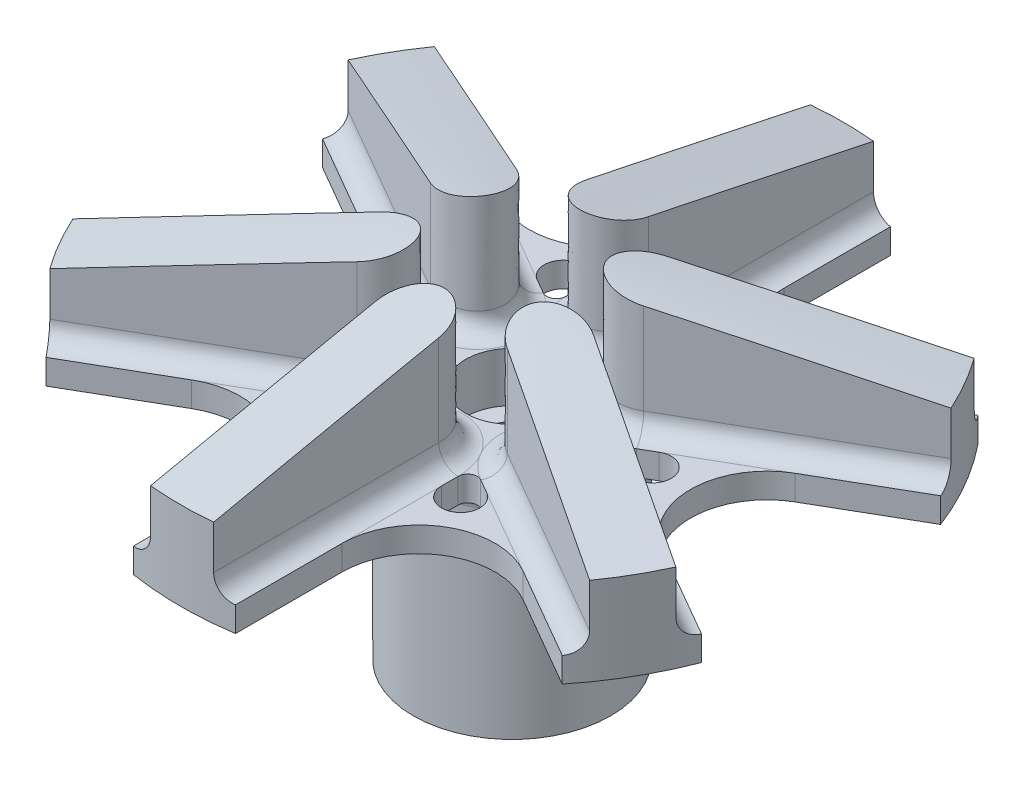
SolidWorks part; units mm, degrees
ref_plane "Front Plane" through (0, 0, 0) normal (0, 0, 1) x (1, 0, 0)
ref_plane "Top Plane" through (0, 0, 0) normal (0, 1, 0) x (1, 0, 0)
ref_plane "Right Plane" through (0, 0, 0) normal (1, 0, 0) x (0, 0, -1)
sketch "Sketch1" plane through (0, 0, 0) normal (0, 1, 0) x (1, 0, 0)
  circle A0 centre (0, 0) radius 26.67
  dimension "D1" = 53.34
extrude "impeller plate" add sketch "Sketch1" along normal blind 2
sketch "Sketch6" plane through (0, 0, 0) normal (0, -1, 0) x (-1, 0, 0)
  circle A0 centre (0, 0) radius 7.9375
  dimension "D1" = 15.875
extrude "boss" add sketch "Sketch6" along normal blind 17
sketch "Sketch7" plane through (0, -17, 0) normal (0, -1, 0) x (-1, 0, 0)
  circle A0 centre (0, 0) radius 2.1828
  dimension "D1" = 4.3656
extrude "bolt bore" cut sketch "Sketch7" against normal through all
sketch "Sketch8" plane through (0, -17, 0) normal (0, -1, 0) x (-1, 0, 0)
  circle A0 centre (0, 0) radius 4
  dimension "D1" = 8
extrude "shaft bore" cut sketch "Sketch8" against normal blind 12
sketch "Sketch9" plane through (0, 2, 0) normal (0, 1, 0) x (1, 0, 0)
  circle A0 centre (0, 0) radius 3.75
  dimension "D1" = 7.5
extrude "bolt head bore" cut sketch "Sketch9" against normal blind 4
sketch "Sketch11" plane through (0, -17, 0) normal (0, -1, 0) x (1, 0, 0)
  line L1 (-6, 1) -> (6, 1)
  line L2 (-6, 1) -> (-6, -1)
  line L3 (-6, -1) -> (6, -1)
  line L4 (6, 1) -> (6, -1)
  line L5 (-6, 1) -> (6, -1) construction
  line L6 (-6, -1) -> (6, 1) construction
  point P0 (0, 0)
  dimension "D1" = 12
  dimension "D2" = 2
extrude "dowel slot" cut sketch "Sketch11" against normal blind 3
sketch "Sketch12" plane through (0, 2, 0) normal (0, 1, 0) x (1, 0, 0)
  line L0 (0, 0) -> (26.67, 0) construction
  line L1 (5.2327, 1.5626) -> (26.6242, 1.5626)
  line L2 (5.2327, -1.5626) -> (26.6242, -1.5626)
  circle A0 centre (0, 0) radius 26.67 construction
  arc A3 (26.6242, -1.5626) -> (26.6242, 1.5626) centre (0, 0) ccw
  arc A4 (5.2327, -1.5626) -> (5.2327, 1.5626) centre (0, 0) ccw
  dimension "D3" = 10.922
  dimension "D1" = 1.5626
  dimension "D2" = 1.5626
extrude "opening alingment cut" cut sketch "Sketch12" against normal blind 1
pattern_circular "opening alingment pattern" count 6 over 360 about axis through (0, 2, 0) along (0, 1, 0) of "opening alingment cut"
sketch "Sketch14" plane through (0, 2, 0) normal (0, 1, 0) x (1, 0, 0)
  line L0 (0, 0) -> (26.67, 0) construction
  line L1 (26.6242, 1.5626) -> (5.2327, 1.5626) construction
  line L3 (24.2619, 11.0747) -> (8.5761, 2.0185) construction
  line L5 (0, 0) -> (23.0969, 13.335) construction
  line L7 (6.0361, 6.4179) -> (21.7219, 15.4741)
  line L9 (8.5761, 2.0185) -> (24.2619, 11.0747)
  arc A2 (26.6242, -1.5626) -> (26.6242, 1.5626) centre (0, 0) ccw construction
  arc A5 (26.6242, 1.5626) -> (14.6654, 22.2759) centre (0, 0) ccw construction
  circle A6 centre (0, 0) radius 5.461 construction
  circle A7 centre (0, 0) radius 5.461 construction
  arc A8 (24.2619, 11.0747) -> (21.7219, 15.4741) centre (0, 0) ccw
  ellipse E0 centre (7.3061, 4.2182) end of major axis (4.7294, 2.7305) minor radius 2.54 (6.0361, 6.4179) -> (8.5761, 2.0185) ccw
  dimension "D1" = 30
  dimension "D2" = 5.08
extrude "one blade" add sketch "Sketch14" along normal blind 9.5881
sketch "Sketch15" plane through (0, 2, 0) normal (0, 1, 0) x (1, 0, 0)
  line L0 (4.8106, 5.2069) -> (14.6654, 22.2759) construction
  line L1 (21.7219, 15.4741) -> (6.0361, 6.4179) construction
  circle A0 centre (0, 0) radius 26.67
  arc A1 (-26.6242, -1.5626) -> (-14.6654, -22.2759) centre (0, 0) ccw construction
  circle A2 centre (0, 0) radius 3.75
  circle A3 centre (0, 0) radius 3.75 construction
  arc A4 (-3.873, -1) -> (3.873, -1) centre (0, 0) ccw construction
extrude "opening alignment fill" add sketch "Sketch15" against normal blind 2
pattern_circular "CirPattern2" count 6 over 360 about axis through (0, 2, 0) along (0, 1, 0) of "one blade"
sketch "Sketch16" plane through (0, 0, 0) normal (1, 0, 0) x (0, 0, -1)
  line L0 (0, 0) -> (0, 11.5881) construction
  line L2 (26.67, 0) -> (26.67, 7.08) construction
  line L3 (0, 11.5881) -> (5.461, 11.5881) construction
  line L4 (5.461, 11.5881) -> (26.67, 7.08)
  line L5 (26.67, 7.08) -> (26.67, 11.5881)
  line L6 (26.67, 11.5881) -> (5.461, 11.5881)
  line L7 (-26.67, 0) -> (26.67, 0) construction
  dimension "D1" = 7.08
  dimension "D2" = 5.461
  dimension "D3" = 26.67
  dimension "D4" = 11.5881
revolve "angle cut" cut sketch "Sketch16" angle 360 about L0
fillet "Fillet1" radius 1.5626 18 edges at (-16.419, 2, -6.5466) (-4.7294, 2, -2.7305) (-2.54, 2, -17.4926) (0, 2, -5.461) (16.419, 2, -6.5466) (4.7294, 2, -2.7305) (13.879, 2, 10.946) (4.7294, 2, 2.7305) (-13.879, 2, 10.946) (-16.419, 2, 6.5466) (-2.54, 2, 17.4926) (0, 2, 5.461) (-13.879, 2, -10.946) (2.54, 2, -17.4926) (13.879, 2, -10.946) (16.419, 2, 6.5466) (-4.7294, 2, 2.7305) (2.54, 2, 17.4926)
sketch "Sketch18" plane through (0, 2, 0) normal (0, 1, 0) x (1, 0, 0)
  line L0 (-20.7707, -16.7293) -> (-13.335, -12.4363)
  line L1 (4.1026, -26.3526) -> (4.1026, -17.7666)
  line L2 (4.1026, -8.4364) -> (4.1026, -26.3526) construction
  line L3 (20.7707, -16.7293) -> (13.335, -12.4363)
  line L4 (20.7707, -16.7293) -> (5.2548, -7.7712) construction
  line L5 (-4.1026, -26.3526) -> (-4.1026, -17.7666)
  line L6 (-24.8733, 9.6233) -> (-17.4376, 5.3303)
  line L7 (-24.8733, -9.6233) -> (-17.4376, -5.3303)
  line L8 (-4.1026, 26.3526) -> (-4.1026, 17.7666)
  line L9 (-20.7707, 16.7293) -> (-13.335, 12.4363)
  line L10 (20.7707, 16.7293) -> (13.335, 12.4363)
  line L11 (4.1026, 26.3526) -> (4.1026, 17.7666)
  line L12 (24.8733, -9.6233) -> (17.4376, -5.3303)
  line L13 (24.8733, 9.6233) -> (17.4376, 5.3303)
  line L14 (5.6414, -9.7711) -> (7.1801, -12.4363) construction
  line L15 (5.2548, -7.7712) -> (6.4107, -8.4386)
  line L16 (4.1026, -8.4364) -> (4.1026, -9.7711)
  line L17 (-4.1026, -8.4364) -> (-4.1026, -9.7711)
  line L18 (-5.2548, -7.7712) -> (-6.4107, -8.4386)
  line L19 (-9.3575, -0.6652) -> (-10.5134, -1.3326)
  line L20 (-9.3575, 0.6652) -> (-10.5134, 1.3326)
  line L21 (-5.2548, 7.7712) -> (-6.4107, 8.4386)
  line L22 (-4.1026, 8.4364) -> (-4.1026, 9.7711)
  line L23 (4.1026, 8.4364) -> (4.1026, 9.7711)
  line L24 (5.2548, 7.7712) -> (6.4107, 8.4386)
  line L25 (9.3575, 0.6652) -> (10.5134, 1.3326)
  line L26 (9.3575, -0.6652) -> (10.5134, -1.3326)
  arc A0 (4.1026, -17.7666) -> (13.335, -12.4363) centre (10.2575, -17.7666) cw
  arc A1 (4.1026, -26.3526) -> (20.7707, -16.7293) centre (0, 0) ccw
  circle A2 centre (10.2575, -17.7666) radius 6.1549 construction
  arc A3 (-20.7707, -16.7293) -> (-4.1026, -26.3526) centre (0, 0) ccw
  arc A4 (-13.335, -12.4363) -> (-4.1026, -17.7666) centre (-10.2575, -17.7666) cw
  arc A5 (-24.8733, 9.6233) -> (-24.8733, -9.6233) centre (0, 0) ccw
  arc A6 (-17.4376, 5.3303) -> (-17.4376, -5.3303) centre (-20.5151, 0) cw
  arc A7 (-4.1026, 26.3526) -> (-20.7707, 16.7293) centre (0, 0) ccw
  arc A8 (-4.1026, 17.7666) -> (-13.335, 12.4363) centre (-10.2575, 17.7666) cw
  arc A9 (20.7707, 16.7293) -> (4.1026, 26.3526) centre (0, 0) ccw
  arc A10 (13.335, 12.4363) -> (4.1026, 17.7666) centre (10.2575, 17.7666) cw
  arc A11 (24.8733, -9.6233) -> (24.8733, 9.6233) centre (0, 0) ccw
  arc A12 (17.4376, -5.3303) -> (17.4376, 5.3303) centre (20.5151, 0) cw
  arc A13 (4.1026, -9.7711) -> (6.4107, -8.4386) centre (5.6414, -9.7711) ccw
  arc A14 (5.2548, -7.7712) -> (4.1026, -8.4364) centre (4.8708, -8.4364) ccw
  arc A15 (-6.4107, -8.4386) -> (-4.1026, -9.7711) centre (-5.6414, -9.7711) ccw
  arc A16 (-4.1026, -8.4364) -> (-5.2548, -7.7712) centre (-4.8708, -8.4364) ccw
  arc A17 (-10.5134, 1.3326) -> (-10.5134, -1.3326) centre (-11.2827, 0) ccw
  arc A18 (-9.3575, -0.6652) -> (-9.3575, 0.6652) centre (-9.7415, 0) ccw
  arc A19 (-4.1026, 9.7711) -> (-6.4107, 8.4386) centre (-5.6414, 9.7711) ccw
  arc A20 (-5.2548, 7.7712) -> (-4.1026, 8.4364) centre (-4.8708, 8.4364) ccw
  arc A21 (6.4107, 8.4386) -> (4.1026, 9.7711) centre (5.6414, 9.7711) ccw
  arc A22 (4.1026, 8.4364) -> (5.2548, 7.7712) centre (4.8708, 8.4364) ccw
  arc A23 (10.5134, -1.3326) -> (10.5134, 1.3326) centre (11.2827, 0) ccw
  arc A24 (9.3575, 0.6652) -> (9.3575, -0.6652) centre (9.7415, 0) ccw
  spline S0 degree 3 poles (5.2548, -7.7712) (4.8829, -7.5565) (4.54, -7.295) (3.9364, -6.6984) (3.6698, -6.3563) (3.4573, -5.9882) knots 0 0 0 0 0.5 0.5 1 1 1 1 construction
  spline S1 degree 3 poles (3.4573, -5.9882) (3.5634, -6.1719) (3.6568, -6.3628) (3.8185, -6.7587) (3.8868, -6.9643) (4.0486, -7.5836) (4.1026, -8.0054) (4.1026, -8.4364) knots 0 0 0 0 0.25 0.25 0.5 0.5 1 1 1 1 construction
  point P16 (6.4107, -11.1037)
  point P85 (0, 0)
  dimension "D1" = 6
extrude "Cut-Extrude1" cut sketch "Sketch18" against normal through all
fillet "Fillet3" radius 1.016 1 edges at (0, 0, 7.9375)
equation "\"z\" = 6\t\t\t\t'number of blades"
equation "\"de_length\" = 10mm\t\t'entrance eye consistent length"
equation "\"av\" = \"ae\"*\"av_ratio\"\t\t'area between just two blades"
equation "\"d2\" = 2.1in \t\t\t'outer diameter of the impeller"
equation "\"theta\" = 12\t\t\t'angle of blades from inner to outer "
equation "\"b2\" = .2in\t\t\t'tip height from disc surface at d2; slightly higher than d_exit"
equation "\"b1\" = \"b2\" + (\"d2\"/2 - \"de\"/2)*tan(\"theta\") \t\t\t'tip height from disc surface at inlet eye"
equation "\"impeller base thickness\"= 2mm"
equation "\"impeller dowel diameter\" = 2mm"
equation "\"impeller bolt head diameter\" = \"m4 head bore diameter\""
equation "\"impeller bolt head depth\" = 4mm"
equation "\"impeller bolt stop depth\" = 3mm"
equation "\"impeller bolt bore\" = \"m4 clearance\""
equation "\"impeller shaft bore depth\" = 12mm"
equation "\"impeller shaft bore\" = 8mm"
equation "\"impeller boss depth\" = \"impeller shaft bore depth\"+\"impeller bolt stop depth\"+\"impeller bolt head depth\"-\"impeller base thickness\""
equation "\"impeller boss diameter\" = \"upper seal ID\""
equation "\"impeller dowel length\" = 2mm*2 + \"impeller shaft bore\""
equation "\"D1@Sketch1\"=\"d2\""
equation "\"D1@impeller plate\" = \"impeller base thickness\""
equation "\"D1@Sketch6\"=\"impeller boss diameter\""
equation "\"D1@boss\" = \"impeller boss depth\""
equation "\"D1@Sketch7\"=\"impeller bolt bore\""
equation "\"D1@Sketch8\"= \"impeller shaft bore\""
equation "\"D1@shaft bore\" = \"impeller shaft bore depth\""
equation "\"D1@Sketch9\"=\"impeller bolt head diameter\""
equation "\"D1@bolt head bore\" = \"impeller bolt head depth\""
equation "\"D1@Sketch11\"=\"impeller dowel length\""
equation "\"D2@Sketch11\"=\"impeller dowel diameter\""
equation "\"D1@dowel slot\" = \"impeller dowel diameter\" + 1mm"
equation "\"ae\" = 3.14*(\"de\"^2)/4\t\t'entrance eye area'"
equation "\"av_ratio\" = .32\t\t'ratio of av/ae at N_s of 470, range is .275 to .375, .325 ideal. High ratio means bigger area means smaller blades"
equation "\"s_open\" = \"av\"/\"b1\"\t\t'width of open area"
equation "\"de\" = 0.43in\t\t\t'entrance eye diameter"
equation "\"ce\" = 3.14*\"de\"\t\t'entrance eye circumference"
equation "\"D1@Sketch12\"=\"s_open\"/2"
equation "\"D3@Sketch12\"=\"de\""
equation "\"D1@opening alingment pattern\" = \"z\""
equation "\"D2@Sketch12\"=\"s_open\"/2"
equation "\"D1@one blade\" = \"b1\""
equation "\"D1@opening alignment fill\" = \"impeller base thickness\""
equation "\"D1@CirPattern2\"=\"z\""
equation "\"D1@Sketch16\"=\"impeller base thickness\"+\"b2\""
equation "\"D2@Sketch16\"=\"de\"/2"
equation "\"D3@Sketch16\"=\"d2\"/2"
equation "\"D1@Sketch14\"=360/\"z\"/2"
equation "\"D4@Sketch16\"=\"b1\"+\"impeller base thickness\""
equation "\"s\"=\"ce\" - \"z\"*\"s_open\""
equation "\"upper seal ID\"= 0.625in"
equation "\"m4 clearance\" = 0.171875in \t'this is 11/64 bit for 4.36mm"
equation "\"m4 tap\" = 0.125in\t\t'this is 1/8 bit for 3.17mm"
equation "\"m4 head bore diameter\" = 7.5mm"
equation "\"m4 head bore depth\" = 5mm\t'actual is ~4mm"
equation "\"d_exit\" = 0.18in \t\t'throat aka d1"
equation "\"bearing OD\" = 30mm"
equation "\"bearing ID\"= 10mm"
equation "\"bearing depth\"= 9mm"
equation "\"bearing outer race thickness\"= 1mm"
equation "\"bearing inner race thickness\"= 1mm"
equation "\"bearing bore\" = \"bearing depth\" + 1mm"
equation "\"lower seal OD\" = .917in\t\t'this is https://www.mcmaster.com/#9281k121/=174001b"
equation "\"lower seal ID\"= .375in"
equation "\"lower seal depth\" = .625in + .218in"
equation "\"lower seal bore\" = \"lower seal depth\" + 1mm"
equation "\"upper seal OD\" = 1.125in\t'this is https://www.mcmaster.com/#5154t33/=173zuau, needs to be visually inspected before machining!"
equation "\"upper seal depth\"= .25in\t'aka height; these values need to be confirmed by inspection!! We may want to compress the height."
equation "\"upper seal bore\" = \"upper seal depth\" + 1mm"
equation "\"big o-ring thickness\" = .139in"
equation "\"big o-ring OD\" = 2.734in"
equation "\"big o-ring ID\" = 3.012in"
equation "\"big o-ring groove depth\" = \"big o-ring thickness\"*4/5"
equation "\"impeller center height\" = \"impeller base thickness\" + \"b1\"\t'impeller height at de"
equation "\"impeller outer height\" = \"impeller base thickness\" + \"b2\"\t'impeller height at de"
equation "\"impeller upper clearance\"= .5mm"
equation "\"impeller horizontal clearance\"= (\"d2\"*1.15 - \"d2\")/2 \t\t'clearance based on D2-D3 ratio for circular volute, ranges 1.15 to 1.2"
equation "\"impeller bottom clearance\"= .5mm"
equation "\"coupler motor shaft hole ID\"= 8mm"
equation "\"coupler OD\"= 17mm"
equation "\"coupler length\"= 25mm"
equation "\"motor OD\" = 64mm"
equation "\"motor shaft diameter\"= 8mm"
equation "\"motor shaft pride\"= 32mm"
equation "\"motor to bearing plate distance\" = \"motor shaft pride\" + 2mm +\"coupler length\"/2"
equation "\"square plate bolt bore\" = 8mm"
equation "\"square plate bolt head diameter\" = 13.5mm"
equation "\"square plate bolt head depth\" = 8mm"
equation "\"square plate bolt pattern diameter\"= 3.5in"
equation "\"motor mount center bore\"= \"coupler OD\"+ 4mm"
equation "\"motor mount post radius\"= ( 3 * \"square plate bolt bore\" ) / 2"
equation "\"motor mount m4 screw hole diameter\"= 4mm"
equation "\"motor mount m4 head diameter\"= 7.25mm"
equation "\"motor mount m4 head depth\"= 4mm"
equation "\"motor mount m4 pattern diamater\" = 30mm"
equation "\"motor mount plate thickness\"= 8mm + \"motor mount m4 head depth\""
equation "\"bearing plate stop ID\" = \"bearing OD\" - 4mm"
equation "\"bearing plate stop depth\" = 3mm"
equation "\"lower seal plate lip depth\" = 2mm"
equation "\"lower seal plate lip ID\" = \"lower seal OD\" - 3mm"
equation "\"lower seal plate thickness\" = \"lower seal plate lip depth\" + \"lower seal bore\""
equation "\"shaft coupler section diameter\" = 8mm"
equation "\"shaft coupler section length\" = \"motor to bearing plate distance\" - \"motor shaft pride\" - 2mm"
equation "\"shaft bearing section diameter\" = \"bearing ID\""
equation "\"shaft bearing section length\" = \"bearing plate stop depth\" + \"bearing depth\""
equation "\"shaft bearing stop diameter\" = \"bearing ID\" + 4mm"
equation "\"shaft bearing stop length\" = 3mm"
equation "\"shaft lower seal section diameter\" = \"lower seal ID\""
equation "\"shaft lower seal section length\" = \"lower seal plate thickness\" + 1mm"
equation "\"shaft impeller section diameter\" = \"impeller shaft bore\""
equation "\"upper seal plate lip ID\" = \"upper seal OD\" - 3mm"
equation "\"upper seal plate pressure hole diameter\" = .125in\t'this is 1/8 drill "
equation "\"upper seal plate pressure tap diameter\" = .328125in \t'this is 21/64 drill for a 1/8 ANPT tap"
equation "\"upper seal plate pressure tap grip\" = 4mm\t\t'this is the area around the tap so it doesn't crack"
equation "\"upper seal plate pressure tap depth\" = 12"
equation "\"impeller cavity center height\"= \"impeller bottom clearance\" + \"impeller upper clearance\" + \"impeller center height\""
equation "\"impeller cavity diameter\"= 2 * \"impeller horizontal clearance\" + \"d2\" \t\t\t\t\t\t\t\t\t'called D3 analytically"
equation "\"impeller cavity outer height\"= \"impeller bottom clearance\" + \"impeller upper clearance\" + \"impeller base thickness\" + \"b2\" \t\t'this is height at impeller diameter d2, not at d3"
equation "\"impeller housing diameter\" = \"square plate bolt pattern diameter\" + 2*\"motor mount post radius\""
equation "\"impeller housing bolt count\" = 8"
equation "\"impeller housing bolt pattern diameter\" = 3.5in"
equation "\"impeller housing threaded inlet diameter\" = 0.6875in \t\t'this is the 11/16 drill size for 1/2 npt fitting"
equation "\"impeller housing threaded inlet depth\"= 15mm"
equation "\"impeller housing exit threaded diameter\"= 0.6875in \t\t'this is the 11/16 drill size for 1/2 npt fitting"
equation "\"impeller housing exit threaded depth\"= 18mm"
equation "\"impeller housing diffuser conical angle\"=10"
equation "\"impeller housing diffuser tangent angle\"=5"
equation "\"impeller housing diffuser final diameter\" = .5in"
equation "\"impeller housing outlet grip\" = 5mm"
equation "\"end mill size\" = 0.375in\t'for 3/8 endmill"
equation "\"m6 clearance\" = 0.234375in\t'this is 15/64 bit = 5.95mm, could use 6mm bit, B bit for 6.04mm or 1/4 bit for 6.35mm"
equation "\"m6 tap\" = 5mm\t\t\t'5mm is appropriate, could use 13/64 or #5,6,7"
equation "\"m6 head bore diameter\" = 11mm\t\t"
equation "\"m6 head bore depth\" = 7mm\t'actual is 6mm"
equation "\"m8 clearance\" = 0.3125in\t'this is 5/16in for 7.93mm, could use 8mm, O,P, or 21/64"
equation "\"m8 tap\" = 0.265625in\t\t'this is 17/64 for 6.746875mm"
equation "\"m8 head bore diameter\" = 14mm"
equation "\"min blade thickness\" = .2in"
equation "\"bearing plate thickness\" = \"bearing bore\" + \"bearing plate stop depth\" + \"shaft bearing stop length\""
equation "\"shaft impeller section length\" = \"upper seal plate thickness\" + \"upper seal plate riser\" + \"impeller bottom clearance\" + \"impeller base thickness\" - \"impeller bolt head depth\" - \"impeller bolt stop depth\""
equation "\"upper seal plate thickness\" = \"upper seal plate pressure hole diameter\"*3"
equation "\"upper seal plate riser\" = \"impeller housing thickness\"/2 - \"b2\"/2 - \"impeller base thickness\" - \t\"impeller bottom clearance\"\t\t\t'this offsets the gap under the housing"
equation "\"impeller housing thickness\"= \"impeller housing exit threaded diameter\" + 2*\"impeller housing outlet grip\""
equation "\"impeller housing bolt diameter\" = \"m6 clearance\""
equation "\"m8 head bore depth\"= 9mm\t'actual is 8mm"
equation "\"D2@Sketch14\"=\"min blade thickness\""
equation "\"D1@Fillet1\"=\"s_open\"/2"
